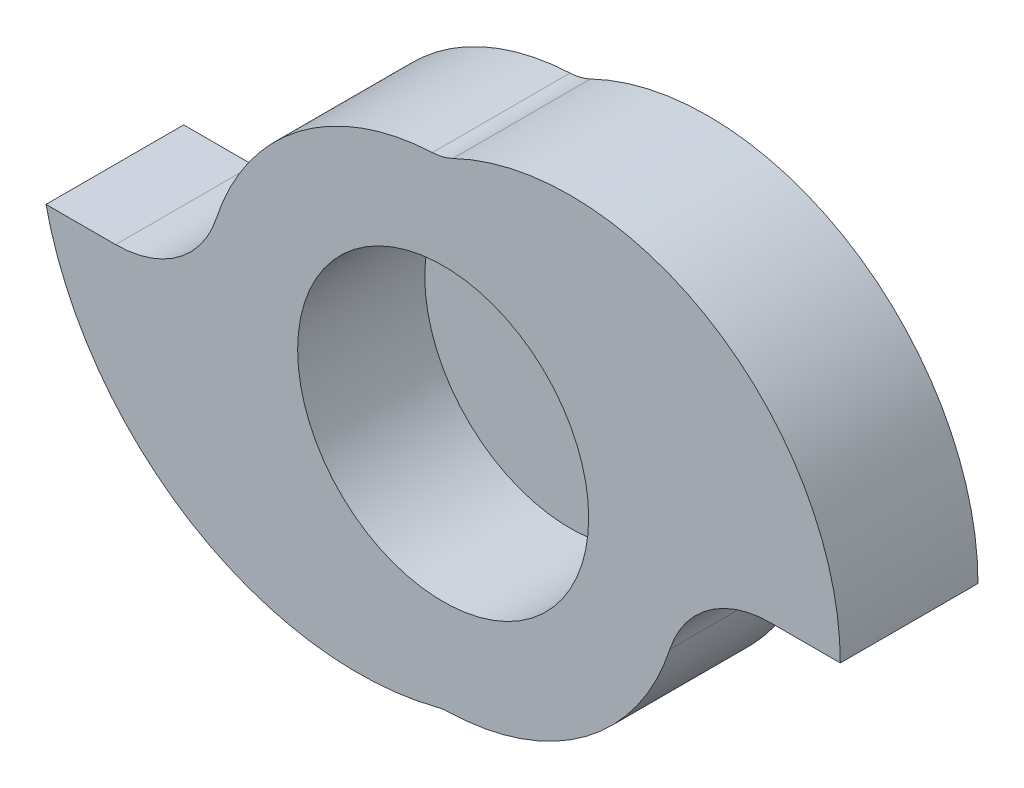
SolidWorks part; units mm, degrees
ref_plane "Front Plane" through (0, 0, 0) normal (0, 0, 1) x (1, 0, 0)
ref_plane "Top Plane" through (0, 0, 0) normal (0, 1, 0) x (1, 0, 0)
ref_plane "Right Plane" through (0, 0, 0) normal (1, 0, 0) x (0, 0, -1)
sketch "Sketch1" plane through (0, 0, 0) normal (0, 0, 1) x (1, 0, 0)
  line L0 (-22.5, 0) -> (-37.5, 0)
  line L1 (22.5, 0) -> (37.5, 0)
  arc A0 (0, 22.5) -> (-22.5, 0) centre (0, 0) ccw
  arc A1 (37.5, 0) -> (0, 22.5) centre (12, 0) ccw
  arc A2 (-37.5, 0) -> (0, -22.5) centre (-8.0723, 6.5462) ccw
  arc A3 (0, -22.5) -> (22.5, 0) centre (0, 0) ccw
  circle A4 centre (0, 0) radius 2.5
  dimension "D1" = 15
  dimension "D3" = 45
  dimension "D2" = 15
extrude "Boss-Extrude1" add sketch "Sketch1" along normal blind 13 contours A3 L1 A1 A0 L0 A2
sketch "Sketch3" plane through (0, 0, 13) normal (0, 0, 1) x (1, 0, 0)
  circle A0 centre (0, 0) radius 13.74
fillet "Fillet1" radius 5 1 edges at (0, 22.5, 6.5)
fillet "Fillet2" radius 10 1 edges at (-22.5, 0, 6.5)
fillet "Fillet3" radius 10 1 edges at (22.5, 0, 6.5)
fillet "Fillet5" radius 5 1 edges at (0, -22.5, 6.5)
extrude "Cut-Extrude2" cut sketch "Sketch3" against normal blind 12 contours A0
sketch "Sketch4" plane through (0, 0, 1) normal (0, 0, 1) x (1, 0, 0)
  line L0 (0, 0) -> (0, 8) construction
  line B0 (-2.5981, 6.5) -> (-5.9782, 12.3546)
  line B1 (5.9782, 12.3546) -> (2.5981, 6.5)
  arc B2 (5.9782, 12.3546) -> (-5.9782, 12.3546) centre (0, 0) ccw
  arc B3 (-2.5496, 6.419) -> (2.5496, 6.419) centre (0, 8) ccw
sketch_block_instance "Block-ribs motor-1"
sketch_block "Block-ribs motor"
sketch "Sketch5" plane through (0, 0, 1) normal (0, 0, 1) x (1, 0, 0)
  line L0 (5.9782, 12.3546) -> (2.5981, 6.5) construction
  line L1 (-2.5981, 6.5) -> (-5.9782, 12.3546) construction
  line L2 (5.9782, 12.3546) -> (2.5981, 6.5)
  line L3 (-2.5981, 6.5) -> (-5.9782, 12.3546)
  line L4 (-2.5981, 6.5) -> (-2.5496, 6.419)
  line L5 (2.5496, 6.419) -> (2.5981, 6.5)
  arc A0 (5.9782, 12.3546) -> (-5.9782, 12.3546) centre (0, 0) ccw construction
  arc A1 (-2.5496, 6.419) -> (2.5496, 6.419) centre (0, 8) ccw construction
  arc A2 (5.9782, 12.3546) -> (-5.9782, 12.3546) centre (0, 0) ccw
  arc A3 (-2.5496, 6.419) -> (2.5496, 6.419) centre (0, 8) ccw
sketch "Sketch6" plane through (0, 0, 0) normal (0, 0, -1) x (-1, 0, 0)
  circle A0 centre (0, 0) radius 2.5
extrude "Cut-Extrude3" cut sketch "Sketch6" against normal up to surface (1 mm away) up to face at (13.74, 0, 1)
